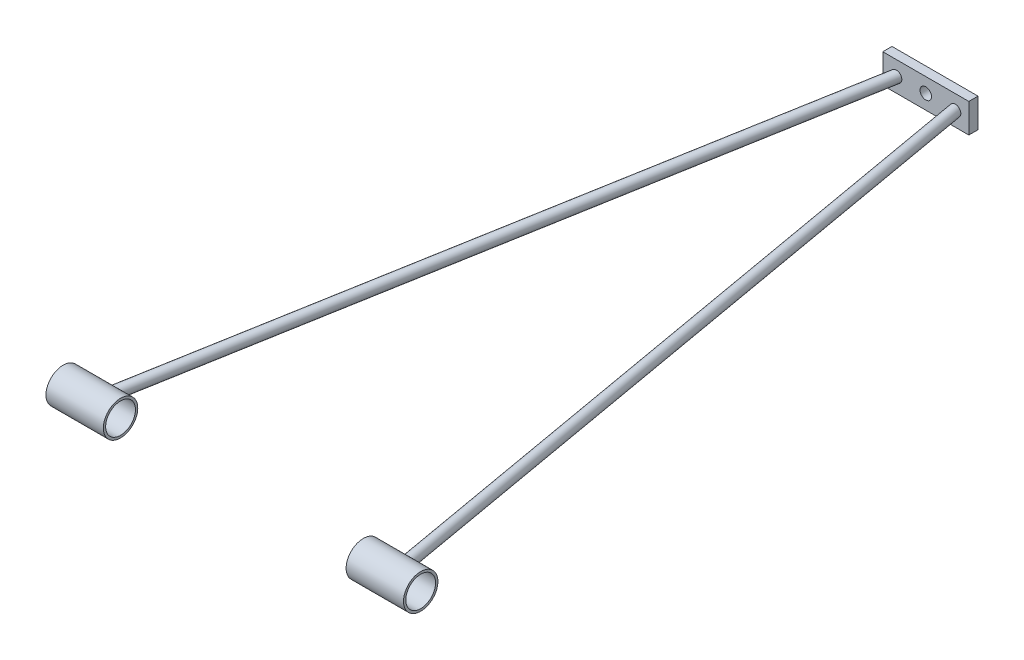
SolidWorks part; units mm, degrees
ref_plane "Front Plane" through (0, 0, 0) normal (0, 0, 1) x (1, 0, 0)
ref_plane "Top Plane" through (0, 0, 0) normal (0, 1, 0) x (1, 0, 0)
ref_plane "Right Plane" through (0, 0, 0) normal (1, 0, 0) x (0, 0, -1)
sketch "Sketch1" plane through (0, 0, 0) normal (0, 1, 0) x (1, 0, 0)
  line L0 (0, -35.7461) -> (0, 70.0445) construction
  line L1 (-130.7962, 0) -> (-25, 600)
  line L2 (130.7962, 0) -> (25, 600)
  line L3 (-12.8708, 600) -> (14.0839, 600) construction
  line L4 (-33.9598, 0) -> (50.1307, 0) construction
  line L5 (-155.7962, 0) -> (-105.7962, 0)
  line L6 (105.7962, 0) -> (155.7962, 0)
  point P11 (-130.7962, 0)
  point P16 (130.7962, 0)
  dimension "D1" = 600
  dimension "D2" = 10
  dimension "D3" = 50
  dimension "D4" = 50
sweep "Sweep2" add path "Sketch1" circular profile diameter 9.525 parameters "D3"=9.525
sketch "Sketch78" plane through (0, 0, 0) normal (0, 1, 0) x (1, 0, 0)
  line L0 (105.7962, 0) -> (155.7962, 0) construction
  line L1 (-155.7962, 0) -> (-105.7962, 0) construction
  line L2 (130.7962, 0) -> (25, 600) construction
  line L3 (-130.7962, 0) -> (-25, 600) construction
  line L4 (105.7962, 0) -> (155.7962, 0)
  line L5 (-155.7962, 0) -> (-105.7962, 0)
  line L6 (130.7962, 0) -> (25, 600)
  line L7 (-130.7962, 0) -> (-25, 600)
sweep "Sweep3" add path "Sketch78" circular profile diameter 9.525 parameters "D3"=9.525
sketch "Sketch87" plane through (0, 0, 0) normal (0, 1, 0) x (1, 0, 0)
  line L0 (105.7962, 0) -> (155.7962, 0) construction
  line L1 (-155.7962, 0) -> (-105.7962, 0) construction
  line L2 (130.7962, 0) -> (25, 600) construction
  line L3 (-130.7962, 0) -> (-25, 600) construction
  line L4 (105.7962, 0) -> (155.7962, 0)
  line L5 (-155.7962, 0) -> (-105.7962, 0)
  line L6 (130.7962, 0) -> (25, 600)
  line L7 (-130.7962, 0) -> (-25, 600)
sweep "Sweep-Thin2" add path "Sketch87" circular profile diameter 30 parameters "D1"=2, "D3"=30
sketch "Sketch140" plane through (0, 0, 0) normal (0, 1, 0) x (1, 0, 0)
  line L0 (-130.7962, 0) -> (-25, 600) construction
  line L1 (130.7962, 0) -> (25, 600) construction
  line L2 (-155.7962, 0) -> (-105.7962, 0) construction
  line L3 (105.7962, 0) -> (155.7962, 0) construction
  line L4 (-130.7962, 0) -> (-25, 600)
  line L5 (130.7962, 0) -> (25, 600)
  line L6 (-155.7962, 0) -> (-105.7962, 0)
  line L7 (105.7962, 0) -> (155.7962, 0)
sweep "Sweep-Thin3" add path "Sketch140" circular profile diameter 30 parameters "D1"=2, "D3"=30
sketch "Sketch161" plane through (0, 0, 0) normal (0, 1, 0) x (1, 0, 0)
  line L0 (105.7962, 0) -> (155.7962, 0) construction
  line L1 (-155.7962, 0) -> (-105.7962, 0) construction
  line L2 (130.7962, 0) -> (25, 600) construction
  line L3 (-130.7962, 0) -> (-25, 600) construction
  line L4 (105.7962, 0) -> (155.7962, 0)
  line L5 (-155.7962, 0) -> (-105.7962, 0)
  line L6 (130.7962, 0) -> (25, 600)
  line L7 (-130.7962, 0) -> (-25, 600)
  line L8 (-25, 600) -> (-25, 595) construction
  line L9 (0, 604) -> (0, 596) construction
  line L10 (-37.5, 604) -> (37.5, 604)
  line L11 (-37.5, 604) -> (-37.5, 596)
  line L12 (-37.5, 596) -> (37.5, 596)
  line L13 (37.5, 604) -> (37.5, 596)
  line L14 (-37.5, 600) -> (37.5, 600) construction
  dimension "D1" = 5
  dimension "D2" = 75
  dimension "D3" = 8
extrude "Boss-Extrude1" add sketch "Sketch161" along normal mid plane 25.4 separate body contours L13 L10 L11 L12 region at (0, 0, -600)
sketch "Sketch164" plane through (-37.5, 0, 0) normal (-1, 0, 0) x (0, 0, 1)
  line L4 (-604, -12.7) -> (-596, -12.7)
  line L5 (-596, -12.7) -> (-596, 12.7)
  line L6 (-596, 12.7) -> (-604, 12.7)
  line L7 (-604, 12.7) -> (-604, -12.7)
  line L8 (-604, -12.7) -> (-596, -12.7)
  line L9 (-596, -12.7) -> (-596, 12.7)
  line L10 (-596, 12.7) -> (-604, 12.7)
  line L11 (-604, 12.7) -> (-604, -12.7)
  dimension "D1" = 0
extrude "Cut-Extrude1" cut sketch "Sketch164" against normal through all
sketch "Sketch165" plane through (-155.7962, 0, 0) normal (-1, 0, 0) x (0, 0, 1)
  circle A0 centre (0, 0) radius 15 construction
  circle A1 centre (0, 0) radius 15
extrude "Cut-Extrude2" cut sketch "Sketch165" against normal through all
sketch "Sketch166" plane through (0, 0, -604) normal (0, 0, -1) x (-1, 0, 0)
  circle A0 centre (0, 0) radius 5
  dimension "D1" = 10
extrude "Cut-Extrude3" cut sketch "Sketch166" against normal blind 25.4
